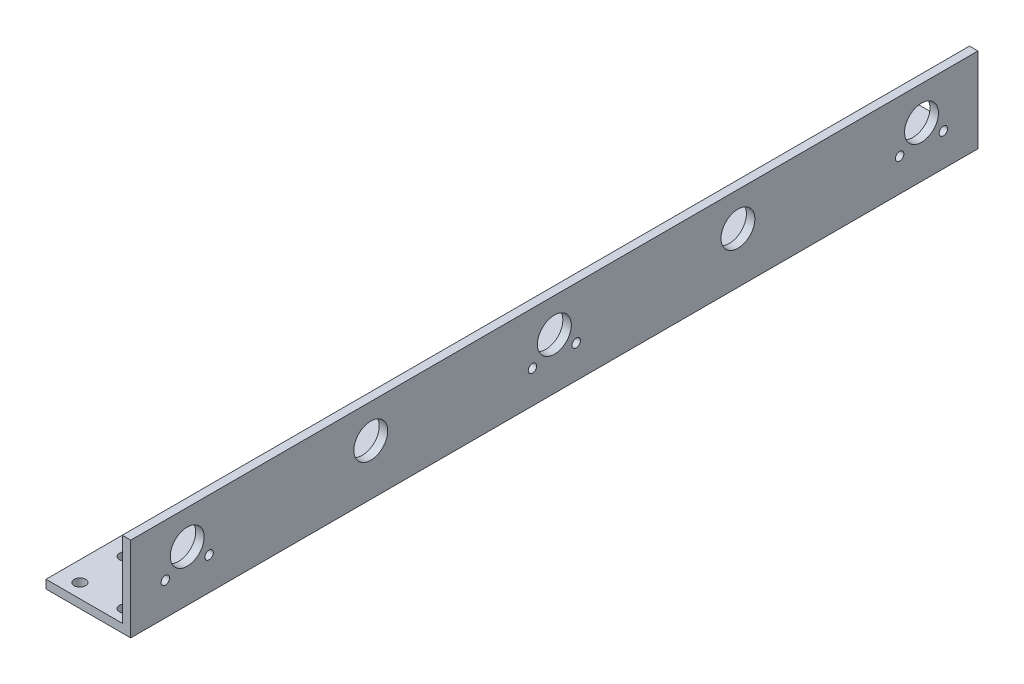
SolidWorks part; units mm, degrees
ref_plane "Front" through (0, 0, 0) normal (0, 0, 1) x (1, 0, 0)
ref_plane "Top" through (0, 0, 0) normal (0, 1, 0) x (1, 0, 0)
ref_plane "Right" through (0, 0, 0) normal (1, 0, 0) x (0, 0, -1)
sketch "草图1" plane through (0, 0, 0) normal (0, 0, 1) x (1, 0, 0)
  line L1 (-15, -15) -> (15, -15)
  line L2 (-15, -15) -> (-15, -12)
  line L3 (12, 15) -> (15, 15)
  line L4 (15, -15) -> (15, 15)
  line L8 (12, 15) -> (12, -12)
  line L9 (-15, -12) -> (12, -12)
  point P0 (0, 0)
extrude "凸台-拉伸1" add sketch "草图1" along normal blind 300
sketch "草图2" plane through (12, 0, 0) normal (-1, 0, 0) x (0, 0, 1)
  circle A0 centre (20, 3) radius 6
  circle A1 centre (85, 3) radius 6
  circle A2 centre (150, 3) radius 6
  circle A3 centre (215, 3) radius 6
  circle A4 centre (280, 3) radius 6
  dimension "D1" = 5
extrude "切除-拉伸1" cut sketch "草图2" against normal blind 300
sketch "草图3" plane through (0, -15, 0) normal (0, -1, 0) x (1, 0, 0)
  line L0 (0, 300) -> (0, 295)
  line L2 (-15, 300) -> (15, 300) construction
  circle A0 centre (8, 5) radius 2
  circle A1 centre (-8, 5) radius 2
  circle A2 centre (-8, 21) radius 2
  circle A3 centre (8, 21) radius 2
  circle A4 centre (8, 295) radius 2
  circle A5 centre (8, 279) radius 2
  circle A6 centre (-8, 279) radius 2
  circle A7 centre (-8, 295) radius 2
  point P21 (0, 13)
  point P30 (0, 287)
  dimension "D1" = 4
  dimension "D2" = 4
extrude "切除-拉伸2" cut sketch "草图3" against normal blind 300 contours A7 | A6 | A5 | A4 | A2 | A1 | A0 | A3 region at (8, -15, 5) region at (-8, -15, 5) region at (-8, -15, 21) region at (8, -15, 21) region at (8, -15, 295) region at (8, -15, 279) region at (-8, -15, 279) region at (-8, -15, 295)
sketch "草图4" plane through (15, 0, 0) normal (1, 0, 0) x (0, 0, -1)
  circle A2 centre (-27.75, -3.4234) radius 1.5
  circle A5 centre (-12.25, -3.4234) radius 1.5
  circle A10 centre (-272.25, -3.4234) radius 1.5
  circle A11 centre (-287.75, -3.4234) radius 1.5
  circle A13 centre (-142.25, -3.4234) radius 1.5
  circle A14 centre (-157.75, -3.4234) radius 1.5
  point P0 (0, 0)
  point P18 (-20, 10)
extrude "切除-拉伸3" cut sketch "草图4" against normal blind 10
